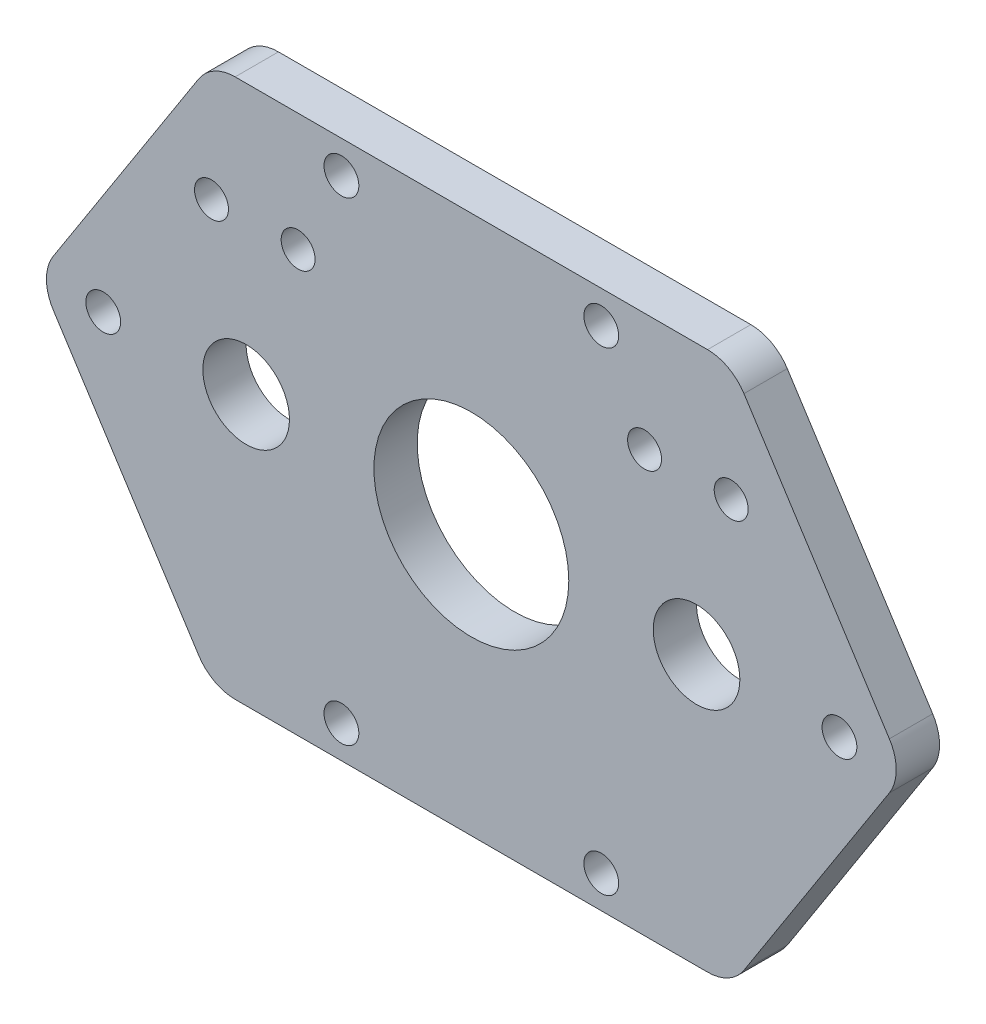
SolidWorks part; units mm, degrees
material "6061-T6 (SS)"
ref_plane "Front Plane" through (0, 0, 0) normal (0, 0, 1) x (1, 0, 0)
ref_plane "Top Plane" through (0, 0, 0) normal (0, 1, 0) x (1, 0, 0)
ref_plane "Right Plane" through (0, 0, 0) normal (1, 0, 0) x (0, 0, -1)
sketch "Sketch5" plane through (0, 0, 0) normal (0, 0, 1) x (1, 0, 0)
  line L0 (-19.7318, -15.9943) -> (19.7318, 15.9943) construction
  line L1 (0, 0) -> (25.4, 0) construction
  line L2 (-19.05, 34.7624) -> (19.05, 34.7624) construction
  line L3 (-38.1, -39.5249) -> (38.1, -39.5249)
  line L4 (-38.1, -39.5249) -> (-38.1, -3.81)
  line L5 (-38.1, 39.5249) -> (38.1, 39.5249)
  line L6 (38.1, -39.5249) -> (38.1, -3.81)
  line L7 (-38.1, -39.5249) -> (38.1, 39.5249) construction
  line L8 (-38.1, 39.5249) -> (38.1, -39.5249) construction
  line L9 (-39.37, 0) -> (39.37, 0) construction
  line L10 (-19.05, -34.7624) -> (19.05, -34.7624) construction
  line L11 (0, 39.5249) -> (0, -39.5249) construction
  line L12 (38.1, -39.5249) -> (-38.1, -39.5249)
  line L16 (-38.1, -12.7) -> (38.1, -12.7) construction
  line L17 (-38.1, -12.7) -> (-38.1, -3.81) construction
  line L18 (-38.1, 12.7) -> (38.1, 12.7) construction
  line L19 (38.1, -12.7) -> (38.1, -3.81) construction
  line L20 (-38.1, -12.7) -> (38.1, 12.7) construction
  line L21 (-38.1, 12.7) -> (38.1, -12.7) construction
  line L22 (-38.1, 39.5249) -> (-63.5, 0)
  line L23 (-38.1, -39.5249) -> (-63.5, 0)
  line L24 (0, 39.5249) -> (0, -39.5249) construction
  line L25 (38.1, -39.5249) -> (63.5, 0)
  line L26 (38.1, 39.5249) -> (63.5, 0)
  line L27 (-38.1, 3.81) -> (-38.1, 39.5249)
  line L28 (-38.1, 3.81) -> (-38.1, 12.7) construction
  line L29 (38.1, 3.81) -> (38.1, 12.7) construction
  line L30 (38.1, 3.81) -> (38.1, 39.5249)
  line L31 (63.5, 0) -> (38.1, -39.5249)
  line L32 (38.1, 39.5249) -> (38.1, -39.5249)
  line L33 (-38.1, 22.225) -> (-25.4, 22.225) construction
  line L38 (-31.75, 12.7) -> (-31.75, 28.575) construction
  line L39 (-55.3386, 12.7) -> (55.3386, 12.7) construction
  line L40 (-19.05, 12.7) -> (-44.45, 12.7) construction
  line L41 (-19.05, 12.7) -> (-19.05, 28.575) construction
  line L42 (-19.05, 28.575) -> (-44.45, 28.575) construction
  line L43 (-44.45, 12.7) -> (-44.45, 28.575) construction
  line L44 (-19.05, 15.875) -> (-44.45, 15.875) construction
  circle A0 centre (0, 0) radius 14.2875
  circle A1 centre (0, 0) radius 25.4 construction
  circle A6 centre (-19.05, 34.7624) radius 2.5527
  circle A7 centre (19.05, 34.7624) radius 2.5527
  circle A8 centre (19.05, -34.7624) radius 2.5527
  circle A9 centre (-19.05, -34.7624) radius 2.5527
  circle A18 centre (53.975, 0) radius 2.5527
  circle A19 centre (-53.975, 0) radius 2.5527
  circle A21 centre (-33.02, 0) radius 6.35
  circle A22 centre (33.02, 0) radius 6.35
  circle A25 centre (-38.1, 22.225) radius 2.4892
  circle A26 centre (-25.4, 22.225) radius 2.4892
  circle A29 centre (25.4, 22.225) radius 2.4892
  circle A30 centre (38.1, 22.225) radius 2.4892
  point P8 (0, 0)
  point P19 (0, 34.7624)
  point P37 (0, -25.4)
  point P59 (-31.75, 22.225)
  point P64 (-43.1128, 28.7091)
  dimension "D1" = 28.575
  dimension "D2" = 5.1054
  dimension "D3" = 50.8
  dimension "D5" = 19.05
  dimension "D6" = 5.1054
  dimension "D8" = 76.2
  dimension "D11" = 12.7
  dimension "D12" = 25.4
  dimension "D13" = 53.975
  dimension "D14" = 53.975
  dimension "D10" = 2
  dimension "D16" = 33.02
  dimension "D17" = 12.7
  dimension "D18" = 4.9784
  dimension "D19" = 9.525
  dimension "D23" = 25.4
  dimension "D4" = 34.7624
  dimension "45" = 39.028
  dimension "D7" = 4.7625
  dimension "D9" = 25.4
  dimension "D15" = 25.4
  dimension "D20" = 3.175
  dimension "D21" = 12.7
  dimension "D22" = 15.875
extrude "Boss-Extrude1" add sketch "Sketch5" along normal blind 6.35 contours L3 | A21 L27 L22 L23 L4 A19 | L6 A22 L30 L5 L27 A21 L4 L3 A9 A0 A6 A7 A8 | L26 L30 A22 L6 L25 A18 region at (-37.002, -21.6675, 0) region at (-46.5386, -0.2237, 0) region at (46.5386, -0.2237, 0)
fillet "Fillet2" radius 6.35 6 edges at (38.1, -39.5249, 3.175) (-38.1, -39.5249, 3.175) (38.1, 39.5249, 3.175) (-38.1, 39.5249, 3.175) (63.5, 0, 3.175) (-63.5, 0, 3.175)
equation "\"NEO\"= 60mm"
